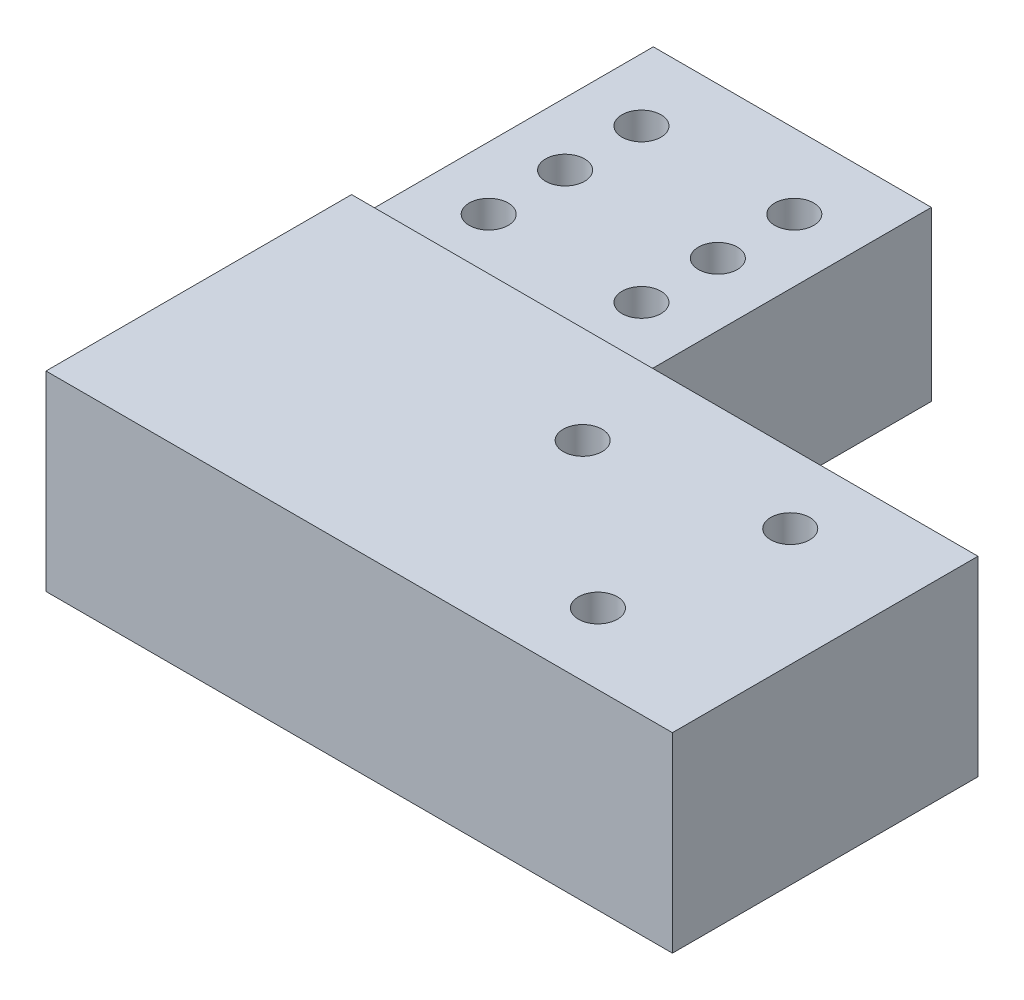
SolidWorks part; units mm, degrees
ref_plane "Front Plane" through (0, 0, 0) normal (0, 0, 1) x (1, 0, 0)
ref_plane "Top Plane" through (0, 0, 0) normal (0, 1, 0) x (1, 0, 0)
ref_plane "Right Plane" through (0, 0, 0) normal (1, 0, 0) x (0, 0, -1)
sketch "Sketch1" plane through (0, 0, 0) normal (0, 1, 0) x (1, 0, 0)
  line L1 (0, 0) -> (36.4, 0)
  line L2 (0, 0) -> (0, 39.5)
  line L3 (0, 39.5) -> (36.4, 39.5)
  line L4 (36.4, 0) -> (36.4, 39.5)
  circle A0 centre (8.2, 29.75) radius 2.55
  circle A1 centre (28.2, 29.75) radius 2.55
  circle A2 centre (28.2, 19.75) radius 2.55
  circle A3 centre (28.2, 9.75) radius 2.55
  circle A4 centre (8.2, 19.75) radius 2.55
  circle A5 centre (8.2, 9.75) radius 2.55
  dimension "D3" = 5.1
  dimension "D1" = 8.2
  dimension "D2" = 9.75
  dimension "D4" = 8.2
  dimension "D5" = 9.75
  dimension "D8" = 20
  dimension "D9" = 39.5
  dimension "D6" = 2
  dimension "D7" = 3
extrude "Boss-Extrude1" add sketch "Sketch1" along normal blind 22
sketch "Sketch2" plane through (0, 22, 0) normal (0, 1, 0) x (1, 0, 0)
  line L1 (0, 39.5) -> (82, 39.5)
  line L2 (0, 39.5) -> (0, 79.5)
  line L3 (0, 79.5) -> (82, 79.5)
  line L4 (82, 39.5) -> (82, 79.5)
  dimension "D1" = 82
  dimension "D2" = 40
extrude "Boss-Extrude2" add sketch "Sketch2" against normal blind 22 and the other way blind 3
mirror "Mirror3" about plane through (0, 22, 0) normal (0, 0, -1) of "Boss-Extrude1", "Boss-Extrude2"
sketch "Sketch7" plane through (0, 25, 0) normal (0, 1, 0) x (1, 0, 0)
  line L0 (66.5819, -48.6599) -> (42.9961, -52.2457)
  line L1 (42.9961, -52.2457) -> (66.5819, -52.2457)
  line L2 (66.5819, -52.2457) -> (66.5819, -48.6599)
  line L3 (42.9961, -52.2457) -> (62.9961, -70.2457)
  line L4 (62.9961, -70.2457) -> (62.9961, -52.2457)
  line L5 (62.9961, -52.2457) -> (42.9961, -52.2457)
  line L6 (66.5819, -48.6599) -> (66.5819, -39.5)
  line L7 (0, -39.5) -> (82, -39.5) construction
  line L8 (66.5819, -39.5) -> (66.5819, -48.6599)
  line L9 (66.5819, -48.6599) -> (82, -48.6599)
  line L10 (82, -39.5) -> (82, -79.5) construction
  dimension "D5" = 9.1599
  dimension "D1" = 18
  dimension "D2" = 23.5858
  dimension "D3" = 3.5858
  dimension "D4" = 3.5858
  dimension "D6" = 15.4181
hole_wizard "Ø5.0mm Dowel Hole1" positions "3DSketch1" profile "Sketch8" hole size "Ø5.0" standard "ANSI Metric" end condition through all
sketch3d "3DSketch1"
  point P0 (42.9961, 25, 52.2457)
  point P3 (62.9961, 25, 70.2457)
  point P7 (66.5819, 25, 48.6599)
sketch "Sketch8" plane through (42.9961, 25, 52.2457) normal (1, 0, 0) x (0, 0, 1)
  line L0 (0, 0) -> (0, 25)
  line L1 (0, 25) -> (2.55, 25)
  line L2 (2.55, 25) -> (2.55, 0)
  line L5 (2.55, 0) -> (0, 0)
  line L11 (0, -6.35) -> (0, 107.95) construction
  dimension "Thru Hole Dia." = 5.1
  dimension "Thru Hole Depth" = 25
sketch "Sketch9" plane through (0, 25, 0) normal (0, 1, 0) x (1, 0, 0)
  line L0 (66.5819, -48.6599) -> (66.5819, -39.5)
  line L1 (0, -39.5) -> (82, -39.5) construction
  line L2 (66.5819, -39.5) -> (82, -39.5)
sketch "Sketch3" plane through (0, 22, 0) normal (0, 1, 0) x (1, 0, 0)
  line L1 (0, 39.5) -> (0, -39.5) construction
  line L4 (0, 0) -> (85.7109, 0)
  line L5 (0, 0) -> (0, 93.142)
  line L6 (0, 93.142) -> (85.7109, 93.142)
  line L7 (85.7109, 0) -> (85.7109, 93.142)
  dimension "D1" = 85.7109
  dimension "D2" = 93.142
extrude "Cut-Extrude1" cut sketch "Sketch3" against normal blind 50 and the other way blind 30
